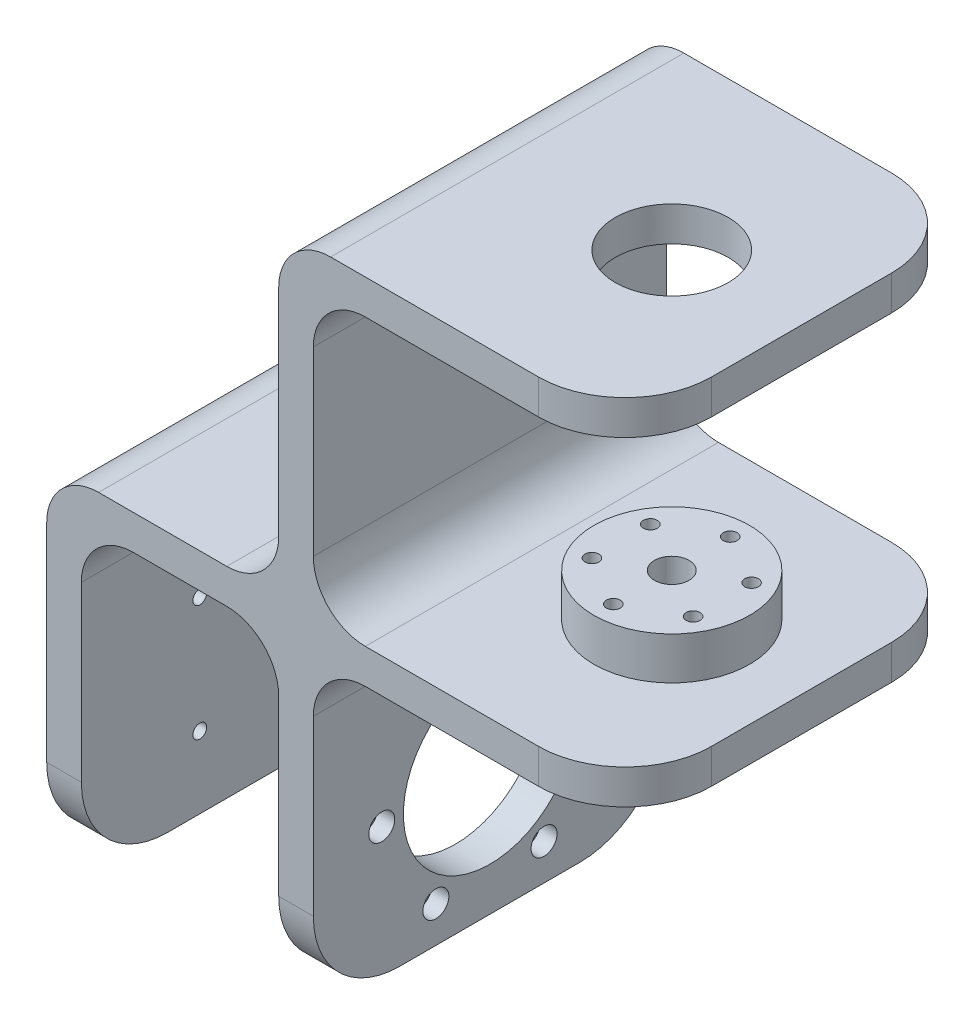
SolidWorks part; units mm, degrees
ref_plane "前视基准面" through (0, 0, 0) normal (0, 0, 1) x (1, 0, 0)
ref_plane "上视基准面" through (0, 0, 0) normal (0, 1, 0) x (1, 0, 0)
ref_plane "右视基准面" through (0, 0, 0) normal (1, 0, 0) x (0, 0, -1)
other "Configuration Table"
sketch "草图1" plane through (0, 0, 0) normal (0, 1, 0) x (1, 0, 0)
  line L1 (40, -40.8) -> (-40, -40.8)
  line L2 (40, -40.8) -> (40, 40.8)
  line L3 (40, 40.8) -> (-40, 40.8)
  line L4 (-40, -40.8) -> (-40, 40.8)
  line L5 (40, -40.8) -> (-40, 40.8) construction
  line L6 (40, 40.8) -> (-40, -40.8) construction
  point P0 (0, 0)
  dimension "D1" = 81.6
  dimension "D2" = 80
extrude "凸台-拉伸1" add sketch "草图1" along normal blind 8
sketch "草图2" plane through (0, 8, 0) normal (0, 1, 0) x (1, 0, 0)
  line L0 (-40, 40.8) -> (-40, -40.8) construction
  line L1 (-32, -40.8) -> (-40, -40.8)
  line L2 (-32, -40.8) -> (-32, 40.8)
  line L3 (-32, 40.8) -> (-40, 40.8)
  line L4 (-40, -40.8) -> (-40, 40.8)
  line L5 (-32, -40.8) -> (-40, 40.8) construction
  line L6 (-32, 40.8) -> (-40, -40.8) construction
  line L7 (40, 40.8) -> (-40, 40.8) construction
  line L8 (-40, -40.8) -> (40, -40.8) construction
  point P0 (-36, 0)
  dimension "D1" = 8
extrude "凸台-拉伸2" add sketch "草图2" along normal blind 52.9
sketch "草图10" plane through (0, 60.9, 0) normal (0, 1, 0) x (1, 0, 0)
  line L0 (-40, -40.8) -> (-40, 40.8) construction
  line L1 (-32, -40.8) -> (-40, -40.8)
  line L2 (-32, -40.8) -> (-32, 40.8)
  line L3 (-32, 40.8) -> (-40, 40.8)
  line L4 (-40, -40.8) -> (-40, 40.8)
  line L5 (-32, -40.8) -> (-40, 40.8) construction
  line L6 (-32, 40.8) -> (-40, -40.8) construction
  line L7 (-32, 40.8) -> (-40, 40.8) construction
  line L8 (-32, -40.8) -> (-32, 40.8) construction
  line L9 (-32, -40.8) -> (-40, -40.8) construction
  point P0 (-36, 0)
extrude "凸台-拉伸7" add sketch "草图10" along normal blind 13
sketch "草图11" plane through (0, 73.9, 0) normal (0, 1, 0) x (1, 0, 0)
  line L0 (-40, -40.8) -> (-40, 40.8) construction
  line L1 (40, -40.8) -> (-40, -40.8)
  line L2 (40, -40.8) -> (40, 40.8)
  line L3 (40, 40.8) -> (-40, 40.8)
  line L4 (-40, -40.8) -> (-40, 40.8)
  line L5 (40, -40.8) -> (-40, 40.8) construction
  line L6 (40, 40.8) -> (-40, -40.8) construction
  line L7 (40, -40.8) -> (40, 40.8) construction
  line L8 (40, 40.8) -> (-40, 40.8) construction
  line L9 (40, -40.8) -> (-40, -40.8) construction
  point P0 (0, 0)
extrude "凸台-拉伸8" add sketch "草图11" along normal blind 8
sketch "草图6" plane through (0, 8, 0) normal (0, 1, 0) x (1, 0, 0)
  line L1 (40, 40.8) -> (-40, 40.8) construction
  line L3 (40, -40.8) -> (40, 40.8) construction
  circle A0 centre (10, 0) radius 18
  point P2 (0, 40.8)
  point P3 (40, 0)
  point P6 (10, 40.8)
  dimension "D3" = 36
  dimension "D1" = 10
extrude "凸台-拉伸4" add sketch "草图6" along normal blind 9.8
sketch "草图4" plane through (0, 8, 0) normal (0, 1, 0) x (1, 0, 0)
  line L2 (40, -40.8) -> (40, 40.8) construction
  line L3 (40, 40.8) -> (-40, 40.8) construction
  circle A0 centre (10, 0) radius 13.5 construction
  circle A1 centre (10, 13.5) radius 1.6
  circle A2 centre (21.6913, 6.75) radius 1.6
  circle A3 centre (21.6913, -6.75) radius 1.6
  circle A4 centre (10, -13.5) radius 1.6
  circle A5 centre (-1.6913, -6.75) radius 1.6
  circle A6 centre (-1.6913, 6.75) radius 1.6
  circle A7 centre (10, 0) radius 4
  point P2 (40, 0)
  point P3 (10, 40.8)
  point P9 (0, 40.8)
  point P21 (10, 0)
  dimension "D1" = 27
  dimension "D4" = 3.2
  dimension "D6" = 8
  dimension "D2" = 10
  dimension "D5" = 6
extrude "切除-拉伸1" cut sketch "草图4" against normal through all and the other way up to next
sketch "草图12" plane through (0, 73.9, 0) normal (0, -1, 0) x (-1, 0, 0)
  circle A0 centre (-10, 0) radius 13.05
  dimension "D1" = 26.1
extrude "切除-拉伸3" cut sketch "草图12" against normal up to next
sketch "草图21" plane through (0, 0, 0) normal (0, -1, 0) x (-1, 0, 0)
  circle A0 centre (-10, -13.5) radius 3
  circle A1 centre (-21.6913, -6.75) radius 3
  circle A2 centre (-21.6913, 6.75) radius 3
  circle A3 centre (-10, 13.5) radius 3
  circle A4 centre (1.6913, 6.75) radius 3
  circle A5 centre (1.6913, -6.75) radius 3
  point P16 (-10, 0)
  dimension "D1" = 6
  dimension "D2" = 6
extrude "切除-拉伸10" cut sketch "草图21" against normal blind 4
sketch "Sketch1" plane through (0, 0, 0) normal (0, -1, 0) x (-1, 0, 0)
  line L0 (-40, 40.8) -> (40, 40.8) construction
  line L1 (40, -40.8) -> (32, -40.8)
  line L2 (40, -40.8) -> (40, 40.8)
  line L3 (40, 40.8) -> (32, 40.8)
  line L4 (32, -40.8) -> (32, 40.8)
  dimension "D1" = 8
extrude "Boss-Extrude1" add sketch "Sketch1" along normal blind 72
sketch "Sketch2" plane through (-40, 0, 0) normal (-1, 0, 0) x (0, 0, 1)
  line L0 (-40.8, 81.9) -> (-40.8, -72) construction
  line L1 (-40.8, 0) -> (40.8, 0)
  line L2 (-40.8, 0) -> (-40.8, 8)
  line L3 (-40.8, 8) -> (40.8, 8)
  line L4 (40.8, 0) -> (40.8, 8)
  line L5 (40.8, 81.9) -> (40.8, -72) construction
  dimension "D1" = 8
extrude "Boss-Extrude2" add sketch "Sketch2" along normal blind 53.6
sketch "Sketch3" plane through (0, 0, 0) normal (0, -1, 0) x (-1, 0, 0)
  line L0 (93.6, 40.8) -> (40, 40.8) construction
  line L1 (93.6, -40.8) -> (85.6, -40.8)
  line L2 (93.6, -40.8) -> (93.6, 40.8)
  line L3 (93.6, 40.8) -> (85.6, 40.8)
  line L4 (85.6, -40.8) -> (85.6, 40.8)
  dimension "D1" = 8
extrude "Boss-Extrude3" add sketch "Sketch3" along normal up to surface (72 mm away) up to face at (-36, -72, 0)
sketch "Sketch4" plane through (-32, 0, 0) normal (1, 0, 0) x (0, 0, -1)
  line L0 (40.8, -72) -> (-40.8, -72) construction
  circle A0 centre (0, -42) radius 20
  circle A2 centre (25, -42) radius 1.6
  circle A3 centre (0, -42) radius 25 construction
  circle A4 centre (12.5, -63.6506) radius 1.6
  circle A5 centre (-12.5, -63.6506) radius 1.6
  circle A6 centre (-25, -42) radius 1.6
  circle A7 centre (-12.5, -20.3494) radius 1.6
  circle A8 centre (12.5, -20.3494) radius 1.6
  point P20 (0, -42)
  dimension "D2" = 40
  dimension "D3" = 3.2
  dimension "D4" = 50
  dimension "D1" = 30
  dimension "D5" = 6
extrude "Cut-Extrude1" cut sketch "Sketch4" against normal up to next
sketch "Sketch5" plane through (-85.6, 0, 0) normal (1, 0, 0) x (0, 0, -1)
  line L0 (40.8, -72) -> (-40.8, -72) construction
  line L1 (0, 0) -> (0, -42) construction
  line L2 (-13.435, -28.565) -> (0, -42) construction
  circle A0 centre (0, -42) radius 19 construction
  circle A1 centre (-13.435, -28.565) radius 1.6
  circle A2 centre (13.435, -28.565) radius 1.6
  circle A3 centre (13.435, -55.435) radius 1.6
  circle A4 centre (-13.435, -55.435) radius 1.6
  point P8 (0, -42)
  point P17 (0, -42)
  dimension "D1" = 38
  dimension "D3" = 3.2
  dimension "D2" = 30
  dimension "D4" = 45
  dimension "D5" = 4
extrude "Cut-Extrude2" cut sketch "Sketch5" against normal up to next
sketch "Sketch6" plane through (-93.6, 0, 0) normal (-1, 0, 0) x (0, 0, 1)
  circle A0 centre (-13.435, -28.565) radius 3
  circle A1 centre (13.435, -28.565) radius 3
  circle A2 centre (13.435, -55.435) radius 3
  circle A3 centre (-13.435, -55.435) radius 3
  point P3 (15.8398, -30.165)
  point P4 (0, -42)
  point P12 (0, -42)
  dimension "D1" = 6
  dimension "D2" = 4
extrude "Cut-Extrude3" cut sketch "Sketch6" against normal blind 4
sketch "Sketch7" plane through (-32, 0, 0) normal (1, 0, 0) x (0, 0, -1)
  circle A0 centre (-12.5, -20.3494) radius 3
  circle A1 centre (12.5, -20.3494) radius 3
  circle A2 centre (25, -42) radius 3
  circle A3 centre (12.5, -63.6506) radius 3
  circle A4 centre (-12.5, -63.6506) radius 3
  circle A5 centre (-25, -42) radius 3
  point P4 (0, -42)
  point P15 (0, -42)
  dimension "D1" = 6
  dimension "D2" = 6
extrude "Cut-Extrude4" cut sketch "Sketch7" against normal blind 4
fillet "Fillet1" radius 12 8 edges at (-85.6, 0, 0) (-40, 0, 0) (-32, 73.9, 0) (-32, 8, 0) (-32, 0, 0) (-40, 8, 0) (-40, 81.9, 0) (-93.6, 8, 0)
fillet "Fillet2" radius 20 8 edges at (-89.6, -72, 40.8) (-89.6, -72, -40.8) (-36, -72, 40.8) (-36, -72, -40.8) (40, 4, 40.8) (40, 4, -40.8) (40, 77.9, 40.8) (40, 77.9, -40.8)
